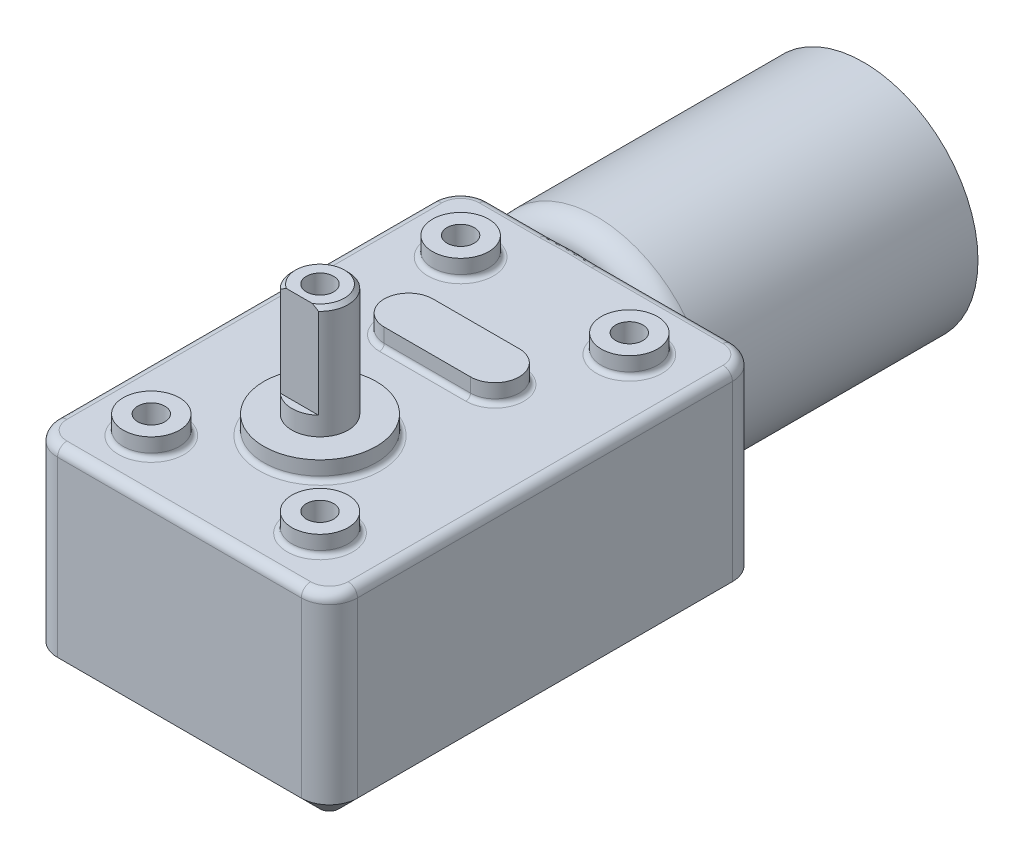
SolidWorks part; units mm, degrees
ref_plane "Front Plane" through (0, 0, 0) normal (0, 0, 1) x (1, 0, 0)
ref_plane "Top Plane" through (0, 0, 0) normal (0, 1, 0) x (1, 0, 0)
ref_plane "Right Plane" through (0, 0, 0) normal (1, 0, 0) x (0, 0, -1)
sketch "Sketch1" plane through (0, 0, 0) normal (0, 1, 0) x (1, 0, 0)
  line L0 (0, -15) -> (0, 31) construction
  line L1 (-13, -15) -> (13, -15)
  line L2 (-16, -12) -> (-16, 28)
  line L3 (-13, 31) -> (13, 31)
  line L4 (16, -12) -> (16, 28)
  circle A0 centre (0, 0) radius 3 construction
  circle A1 centre (-9, 24) radius 3 construction
  circle A2 centre (-9, -9) radius 3 construction
  circle A3 centre (9, -9) radius 3 construction
  circle A4 centre (9, 24) radius 3 construction
  arc A5 (-13, -15) -> (-16, -12) centre (-13, -12) cw
  arc A6 (13, -15) -> (16, -12) centre (13, -12) ccw
  arc A7 (-16, 28) -> (-13, 31) centre (-13, 28) cw
  arc A8 (13, 31) -> (16, 28) centre (13, 28) cw
  dimension "D4" = 6
  dimension "D5" = 6
  dimension "D7" = 3
  dimension "D8" = 3
  dimension "D1" = 33
  dimension "D2" = 9
  dimension "D3" = 7
  dimension "D6" = 9
  dimension "D9" = 46
  dimension "D10" = 32
extrude "Boss-Extrude1" add sketch "Sketch1" along normal blind 21.5
sketch "Sketch2" plane through (0, 21.5, 0) normal (0, 1, 0) x (1, 0, 0)
  circle A0 centre (0, 0) radius 3
extrude "Boss-Extrude2" add sketch "Sketch2" along normal blind 14
sketch "Sketch3" plane through (0, 35.5, 0) normal (0, 1, 0) x (1, 0, 0)
  line L0 (-2.0396, -2.2) -> (2.0396, -2.2)
  circle A0 centre (0, 0) radius 3 construction
  arc A1 (-2.0396, -2.2) -> (2.0396, -2.2) centre (0, 0) ccw
  dimension "D1" = 2.2
extrude "Cut-Extrude1" cut sketch "Sketch3" against normal blind 10
sketch "Sketch4" plane through (0, 21.5, 0) normal (0, 1, 0) x (1, 0, 0)
  line L0 (-4.6012, 14.0529) -> (4.6012, 14.0529) construction
  line L1 (-4.6012, 16.6529) -> (4.6012, 16.6529)
  line L2 (-4.6012, 11.4529) -> (4.6012, 11.4529)
  line L3 (0, -15) -> (0, 31) construction
  circle A0 centre (-9, 24) radius 3
  circle A1 centre (9, 24) radius 3
  circle A2 centre (9, -9) radius 3
  circle A3 centre (-9, -9) radius 3
  circle A4 centre (0, 0) radius 6
  arc A5 (-4.6012, 16.6529) -> (-4.6012, 11.4529) centre (-4.6012, 14.0529) ccw
  arc A6 (4.6012, 11.4529) -> (4.6012, 16.6529) centre (4.6012, 14.0529) ccw
  point P12 (0, 14.0529)
  dimension "D1" = 12
  dimension "D2" = 2.6
extrude "Boss-Extrude3" add sketch "Sketch4" along normal blind 2
ref_plane "Plane1" through (0, 11, 0) normal (0, 1, 0) x (1, 0, 0)
sketch "Sketch5" plane through (0, 11, 0) normal (0, 1, 0) x (1, 0, 0)
  line L0 (-3.8, 29.6479) -> (-3.8, 60.8) construction
  line L1 (-3.8, 31) -> (-13.7, 31)
  line L2 (-3.8, 31) -> (-3.8, 60.8)
  line L3 (-15.75, 61.8) -> (-16, 61.8)
  line L4 (-16, 33.3) -> (-16, 61.8)
  line L5 (-3.8, 61.8) -> (-3.8, 69.8) construction
  line L6 (-15.75, 61.8) -> (-15.75, 60.8)
  line L7 (-15.75, 60.8) -> (-7.3, 60.8)
  line L8 (-6.8, 61.3) -> (-6.8, 61.8)
  line L9 (-6.8, 61.8) -> (-5.3, 61.8)
  line L10 (-3.8, 60.8) -> (-3.8, 61.8)
  line L11 (-5.3, 61.8) -> (-5.3, 65.4)
  line L12 (-4.9, 65.8) -> (-3.8, 65.8)
  line L13 (-3.8, 61.8) -> (-3.8, 65.8)
  line L14 (-13, 31) -> (13, 31) construction
  line L15 (-16, -12) -> (-16, 28) construction
  line L16 (-5.3, 65.4) -> (-4.9, 65.8)
  arc A0 (-13.7, 31) -> (-16, 33.3) centre (-13.7, 33.3) cw
  arc A1 (-7.3, 60.8) -> (-6.8, 61.3) centre (-7.3, 61.3) ccw
  point P16 (-5.3, 65.8)
  dimension "D2" = 2.3
  dimension "D9" = 0.5
  dimension "D1" = 12.2
  dimension "D3" = 0.25
  dimension "D4" = 1
  dimension "D5" = 1.5
  dimension "D6" = 12.2
  dimension "D7" = 3
  dimension "D8" = 4
revolve "Revolve1" add sketch "Sketch5" angle 360 about L2
sketch "Sketch6" plane through (0, 11, 0) normal (0, 1, 0) x (1, 0, 0)
  line L0 (-10.27, 63.8239) -> (-10.27, 63.3236) construction
  line L1 (-11.27, 60.8) -> (-9.27, 60.8)
  line L2 (-11.27, 60.8) -> (-11.27, 63.8239)
  line L3 (-11.27, 63.8239) -> (-9.27, 63.8239) construction
  line L4 (-9.27, 60.8) -> (-9.27, 63.8239)
  line L5 (-9.8226, 63.8239) -> (-9.8226, 63.3236)
  line L6 (-10.7175, 63.8239) -> (-10.7175, 63.3236)
  line L7 (-3.8, 61.8) -> (-3.8, 72.427) construction
  line L8 (3.67, 63.8239) -> (1.67, 63.8239) construction
  line L9 (1.67, 60.8) -> (1.67, 63.8239)
  line L10 (3.67, 60.8) -> (3.67, 63.8239)
  line L11 (3.67, 60.8) -> (1.67, 60.8)
  line L12 (2.67, 63.8239) -> (2.67, 63.3236) construction
  line L13 (2.2226, 63.8239) -> (2.2226, 63.3236)
  line L14 (3.1175, 63.8239) -> (3.1175, 63.3236)
  line L20 (-15.75, 60.8) -> (-7.3, 60.8) construction
  arc A0 (-9.8226, 63.8239) -> (-10.7175, 63.8239) centre (-10.27, 63.8239) ccw
  arc A1 (-10.7175, 63.3236) -> (-9.8226, 63.3236) centre (-10.27, 63.3236) ccw
  arc A2 (1.67, 63.8239) -> (3.67, 63.8239) centre (2.67, 63.8239) cw
  arc A3 (-9.27, 63.8239) -> (-11.27, 63.8239) centre (-10.27, 63.8239) ccw
  arc A4 (2.2226, 63.8239) -> (3.1175, 63.8239) centre (2.67, 63.8239) cw
  arc A5 (3.1175, 63.3236) -> (2.2226, 63.3236) centre (2.67, 63.3236) cw
  point P6 (-10.27, 63.5737)
  point P20 (2.67, 63.5737)
  dimension "D1" = 2
extrude "Boss-Extrude4" add sketch "Sketch6" along normal blind 0.2 and the other way blind 0.2 separate body
fillet "Fillet1" radius 1 8 edges at (-15.1213, 21.5, 14.1213) (-16, 21.5, -8) (-15.1213, 21.5, -30.1213) (0, 21.5, -31) (15.1213, 21.5, -30.1213) (16, 21.5, -8) (15.1213, 21.5, 14.1213) (0, 21.5, 15)
chamfer "Chamfer1" distance 2 angle 45 8 edges at (0, 0, -31) (-15.1213, 0, -30.1213) (15.1213, 0, -30.1213) (-16, 0, -8) (16, 0, -8) (-15.1213, 0, 14.1213) (15.1213, 0, 14.1213) (0, 0, 15)
fillet "Fillet2" radius 0.5 9 edges at (0, 21.5, -11.4529) (-7.2012, 21.5, -14.0529) (0, 21.5, -16.6529) (0, 21.5, -6) (-9, 21.5, 6) (-9, 21.5, -27) (7.2012, 21.5, -14.0529) (9, 21.5, -27) (9, 21.5, 6)
hole_wizard "M3.5x0.6 Tapped Hole1" positions "Sketch8" profile "Sketch7" tap size "M3.5x0.6" standard "ANSI Metric"
sketch "Sketch8" plane through (0, 23.5, 0) normal (0, 1, 0) x (1, 0, 0)
  point P0 (-9, 24)
  point P3 (9, 24)
  point P6 (9, -9)
  point P9 (-9, -9)
sketch "Sketch7" plane through (-9, 23.5, -24) normal (1, 0, 0) x (0, 0, 1)
  line L0 (0, 0) -> (0, 7.8712)
  line L1 (0, 7.8712) -> (1.45, 7)
  line L2 (1.45, 7) -> (1.45, 0)
  line L5 (1.45, 0) -> (0, 0)
  line L10 (0, 7.8712) -> (-1.45, 7) construction
  line L11 (0, -6.35) -> (0, 107.95) construction
  dimension "Tap Drill Dia." = 2.9
  dimension "Tap Drill Depth" = 7
  dimension "Drill Angle" = 118
cosmetic thread "Hole Thread1" parameters "D1"=7, "D2"=3.5
cosmetic thread "Hole Thread2" parameters "D1"=7, "D2"=3.5
cosmetic thread "Hole Thread3" parameters "D1"=7, "D2"=3.5
cosmetic thread "Hole Thread4" parameters "D1"=7, "D2"=3.5
hole_wizard "M3.5x0.6 Tapped Hole2" positions "Sketch10" profile "Sketch9" tap size "M3.5x0.6" standard "ANSI Metric"
sketch "Sketch10" plane through (0, 35.5, 0) normal (0, 1, 0) x (1, 0, 0)
  point P0 (0, 0)
sketch "Sketch9" plane through (0, 35.5, 0) normal (1, 0, 0) x (0, 0, 1)
  line L0 (0, 0) -> (0, 9.6712)
  line L1 (0, 9.6712) -> (1.45, 8.8)
  line L2 (1.45, 8.8) -> (1.45, 0)
  line L5 (1.45, 0) -> (0, 0)
  line L10 (0, 9.6712) -> (-1.45, 8.8) construction
  line L11 (0, -6.35) -> (0, 107.95) construction
  dimension "Tap Drill Dia." = 2.9
  dimension "Tap Drill Depth" = 8.8
  dimension "Drill Angle" = 118
cosmetic thread "Hole Thread5" parameters "D1"=7, "D2"=3.5
chamfer "Chamfer3" distance 0.4 angle 45 1 edges at (0, 35.5, -3)
sketch "Sketch11" plane through (0, 0, 0) normal (0, -1, 0) x (1, 0, 0)
  circle A0 centre (0, 0) radius 6.3267
extrude "Boss-Extrude5" add sketch "Sketch11" along normal blind 1
fillet "Fillet3" radius 0.3 1 edges at (0, 0, -6.3267)
